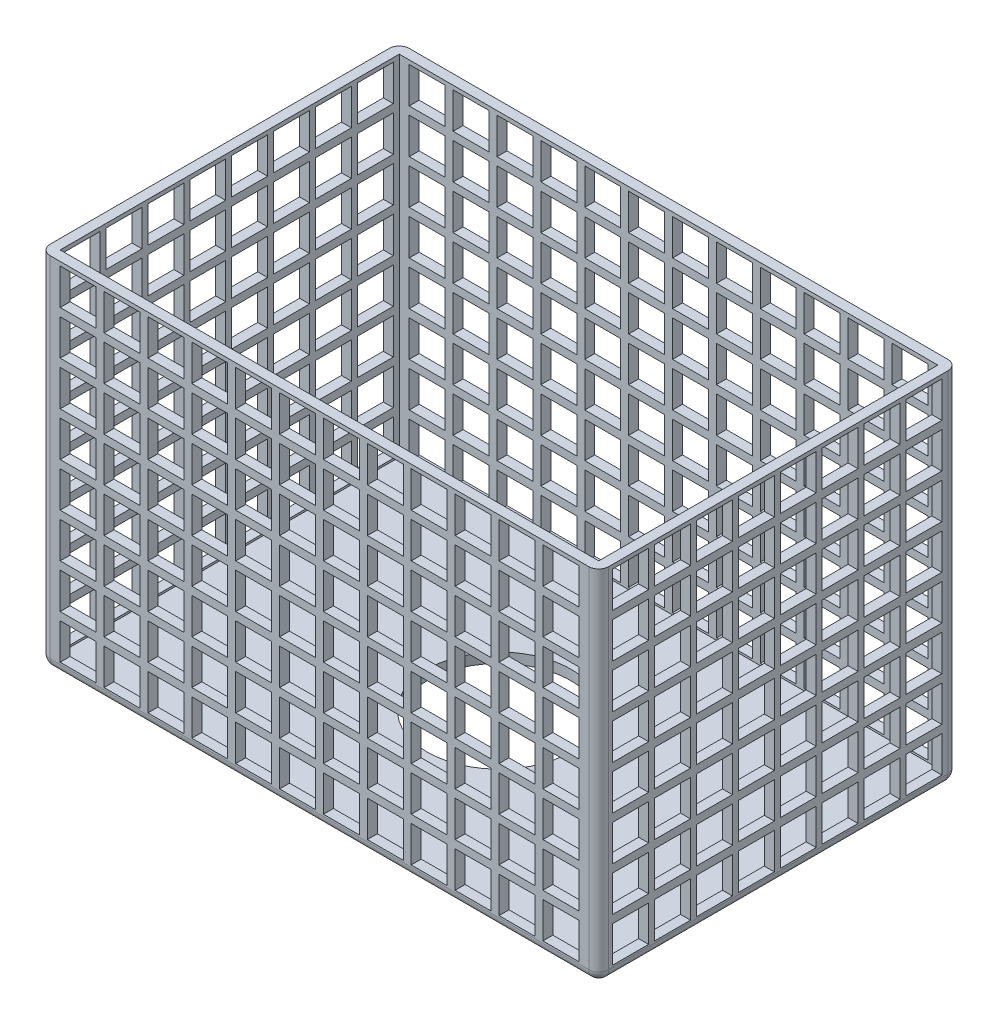
SolidWorks part; units mm, degrees
ref_plane "前视基准面" through (0, 0, 0) normal (0, 0, 1) x (1, 0, 0)
ref_plane "上视基准面" through (0, 0, 0) normal (0, 1, 0) x (1, 0, 0)
ref_plane "右视基准面" through (0, 0, 0) normal (1, 0, 0) x (0, 0, -1)
sketch "草图1" plane through (0, 0, 0) normal (0, 0, 1) x (1, 0, 0)
  line L1 (-140, 90) -> (140, 90)
  line L2 (-140, 90) -> (-140, -90)
  line L3 (-140, -90) -> (140, -90)
  line L4 (140, 90) -> (140, -90)
  line L5 (-140, 90) -> (140, -90) construction
  line L6 (-140, -90) -> (140, 90) construction
  point P0 (0, 0)
  dimension "D1" = 280
  dimension "D2" = 180
extrude "凸台-拉伸1" add sketch "草图1" along normal blind 180
ref_plane "基准面4" through (0, 0, 0) normal (-1, 0, 0) x (0, 0, 1)
ref_plane "基准面5" through (0, 0, 0) normal (0, 1, 0) x (1, 0, 0)
ref_plane "基准面6" through (0, 0, 0) normal (0, 0, -1) x (-1, 0, 0)
fillet "圆角1" radius 5 8 edges at (-140, -90, 90) (-140, 0, 0) (0, -90, 0) (140, 0, 0) (140, -90, 90) (140, 0, 180) (0, -90, 180) (-140, 0, 180)
shell "抽壳1" thickness 5 removed face at (0, 90, 90)
sketch "草图4" plane through (0, 0, 0) normal (0, 0, -1) x (-1, 0, 0)
  line L0 (-135, 90) -> (135, 90) construction
  line L1 (-130, 88) -> (-112, 88)
  line L2 (-130, 88) -> (-130, 70)
  line L3 (-130, 70) -> (-112, 70)
  line L4 (-112, 88) -> (-112, 70)
  line L5 (-135, 90) -> (-135, -85) construction
  line L6 (-108, 88) -> (-108, 70)
  line L7 (-108, 88) -> (-90, 88)
  line L8 (-90, 88) -> (-90, 70)
  line L9 (-108, 70) -> (-90, 70)
  line L10 (-86, 88) -> (-86, 70)
  line L11 (-86, 88) -> (-68, 88)
  line L12 (-68, 88) -> (-68, 70)
  line L13 (-86, 70) -> (-68, 70)
  line L14 (-64, 88) -> (-64, 70)
  line L15 (-64, 88) -> (-46, 88)
  line L16 (-46, 88) -> (-46, 70)
  line L17 (-64, 70) -> (-46, 70)
  line L18 (-42, 88) -> (-42, 70)
  line L19 (-42, 88) -> (-24, 88)
  line L20 (-24, 88) -> (-24, 70)
  line L21 (-42, 70) -> (-24, 70)
  line L22 (-20, 88) -> (-20, 70)
  line L23 (-20, 88) -> (-2, 88)
  line L24 (-2, 88) -> (-2, 70)
  line L25 (-20, 70) -> (-2, 70)
  line L26 (2, 88) -> (2, 70)
  line L27 (2, 88) -> (20, 88)
  line L28 (20, 88) -> (20, 70)
  line L29 (2, 70) -> (20, 70)
  line L30 (24, 88) -> (24, 70)
  line L31 (24, 88) -> (42, 88)
  line L32 (42, 88) -> (42, 70)
  line L33 (24, 70) -> (42, 70)
  line L34 (46, 88) -> (46, 70)
  line L35 (46, 88) -> (64, 88)
  line L36 (64, 88) -> (64, 70)
  line L37 (46, 70) -> (64, 70)
  line L38 (68, 88) -> (68, 70)
  line L39 (68, 88) -> (86, 88)
  line L40 (86, 88) -> (86, 70)
  line L41 (68, 70) -> (86, 70)
  line L42 (90, 88) -> (90, 70)
  line L43 (90, 88) -> (108, 88)
  line L44 (108, 88) -> (108, 70)
  line L45 (90, 70) -> (108, 70)
  line L46 (112, 88) -> (112, 70)
  line L47 (112, 88) -> (130, 88)
  line L48 (130, 88) -> (130, 70)
  line L49 (112, 70) -> (130, 70)
  line L50 (-108, 66) -> (-108, 48)
  line L51 (-108, 66) -> (-90, 66)
  line L52 (-90, 66) -> (-90, 48)
  line L53 (-108, 48) -> (-90, 48)
  line L54 (-86, 66) -> (-86, 48)
  line L55 (-86, 66) -> (-68, 66)
  line L56 (-68, 66) -> (-68, 48)
  line L57 (-86, 48) -> (-68, 48)
  line L58 (-64, 66) -> (-64, 48)
  line L59 (-64, 66) -> (-46, 66)
  line L60 (-46, 66) -> (-46, 48)
  line L61 (-64, 48) -> (-46, 48)
  line L62 (-42, 66) -> (-42, 48)
  line L63 (-42, 66) -> (-24, 66)
  line L64 (-24, 66) -> (-24, 48)
  line L65 (-42, 48) -> (-24, 48)
  line L66 (-20, 66) -> (-20, 48)
  line L67 (-20, 66) -> (-2, 66)
  line L68 (-2, 66) -> (-2, 48)
  line L69 (-20, 48) -> (-2, 48)
  line L70 (2, 66) -> (2, 48)
  line L71 (2, 66) -> (20, 66)
  line L72 (20, 66) -> (20, 48)
  line L73 (2, 48) -> (20, 48)
  line L74 (24, 66) -> (24, 48)
  line L75 (24, 66) -> (42, 66)
  line L76 (42, 66) -> (42, 48)
  line L77 (24, 48) -> (42, 48)
  line L78 (46, 66) -> (46, 48)
  line L79 (46, 66) -> (64, 66)
  line L80 (64, 66) -> (64, 48)
  line L81 (46, 48) -> (64, 48)
  line L82 (68, 66) -> (68, 48)
  line L83 (68, 66) -> (86, 66)
  line L84 (86, 66) -> (86, 48)
  line L85 (68, 48) -> (86, 48)
  line L86 (90, 66) -> (90, 48)
  line L87 (90, 66) -> (108, 66)
  line L88 (108, 66) -> (108, 48)
  line L89 (90, 48) -> (108, 48)
  line L90 (112, 66) -> (112, 48)
  line L91 (112, 66) -> (130, 66)
  line L92 (130, 66) -> (130, 48)
  line L93 (112, 48) -> (130, 48)
  line L94 (-108, 44) -> (-108, 26)
  line L95 (-108, 44) -> (-90, 44)
  line L96 (-90, 44) -> (-90, 26)
  line L97 (-108, 26) -> (-90, 26)
  line L98 (-86, 44) -> (-86, 26)
  line L99 (-86, 44) -> (-68, 44)
  line L100 (-68, 44) -> (-68, 26)
  line L101 (-86, 26) -> (-68, 26)
  line L102 (-64, 44) -> (-64, 26)
  line L103 (-64, 44) -> (-46, 44)
  line L104 (-46, 44) -> (-46, 26)
  line L105 (-64, 26) -> (-46, 26)
  line L106 (-42, 44) -> (-42, 26)
  line L107 (-42, 44) -> (-24, 44)
  line L108 (-24, 44) -> (-24, 26)
  line L109 (-42, 26) -> (-24, 26)
  line L110 (-20, 44) -> (-20, 26)
  line L111 (-20, 44) -> (-2, 44)
  line L112 (-2, 44) -> (-2, 26)
  line L113 (-20, 26) -> (-2, 26)
  line L114 (2, 44) -> (2, 26)
  line L115 (2, 44) -> (20, 44)
  line L116 (20, 44) -> (20, 26)
  line L117 (2, 26) -> (20, 26)
  line L118 (24, 44) -> (24, 26)
  line L119 (24, 44) -> (42, 44)
  line L120 (42, 44) -> (42, 26)
  line L121 (24, 26) -> (42, 26)
  line L122 (46, 44) -> (46, 26)
  line L123 (46, 44) -> (64, 44)
  line L124 (64, 44) -> (64, 26)
  line L125 (46, 26) -> (64, 26)
  line L126 (68, 44) -> (68, 26)
  line L127 (68, 44) -> (86, 44)
  line L128 (86, 44) -> (86, 26)
  line L129 (68, 26) -> (86, 26)
  line L130 (90, 44) -> (90, 26)
  line L131 (90, 44) -> (108, 44)
  line L132 (108, 44) -> (108, 26)
  line L133 (90, 26) -> (108, 26)
  line L134 (112, 44) -> (112, 26)
  line L135 (112, 44) -> (130, 44)
  line L136 (130, 44) -> (130, 26)
  line L137 (112, 26) -> (130, 26)
  line L138 (-108, 22) -> (-108, 4)
  line L139 (-108, 22) -> (-90, 22)
  line L140 (-90, 22) -> (-90, 4)
  line L141 (-108, 4) -> (-90, 4)
  line L142 (-86, 22) -> (-86, 4)
  line L143 (-86, 22) -> (-68, 22)
  line L144 (-68, 22) -> (-68, 4)
  line L145 (-86, 4) -> (-68, 4)
  line L146 (-64, 22) -> (-64, 4)
  line L147 (-64, 22) -> (-46, 22)
  line L148 (-46, 22) -> (-46, 4)
  line L149 (-64, 4) -> (-46, 4)
  line L150 (-42, 22) -> (-42, 4)
  line L151 (-42, 22) -> (-24, 22)
  line L152 (-24, 22) -> (-24, 4)
  line L153 (-42, 4) -> (-24, 4)
  line L154 (-20, 22) -> (-20, 4)
  line L155 (-20, 22) -> (-2, 22)
  line L156 (-2, 22) -> (-2, 4)
  line L157 (-20, 4) -> (-2, 4)
  line L158 (2, 22) -> (2, 4)
  line L159 (2, 22) -> (20, 22)
  line L160 (20, 22) -> (20, 4)
  line L161 (2, 4) -> (20, 4)
  line L162 (24, 22) -> (24, 4)
  line L163 (24, 22) -> (42, 22)
  line L164 (42, 22) -> (42, 4)
  line L165 (24, 4) -> (42, 4)
  line L166 (46, 22) -> (46, 4)
  line L167 (46, 22) -> (64, 22)
  line L168 (64, 22) -> (64, 4)
  line L169 (46, 4) -> (64, 4)
  line L170 (68, 22) -> (68, 4)
  line L171 (68, 22) -> (86, 22)
  line L172 (86, 22) -> (86, 4)
  line L173 (68, 4) -> (86, 4)
  line L174 (90, 22) -> (90, 4)
  line L175 (90, 22) -> (108, 22)
  line L176 (108, 22) -> (108, 4)
  line L177 (90, 4) -> (108, 4)
  line L178 (112, 22) -> (112, 4)
  line L179 (112, 22) -> (130, 22)
  line L180 (130, 22) -> (130, 4)
  line L181 (112, 4) -> (130, 4)
  line L182 (-108, 0) -> (-108, -18)
  line L183 (-108, 0) -> (-90, 0)
  line L184 (-90, 0) -> (-90, -18)
  line L185 (-108, -18) -> (-90, -18)
  line L186 (-86, 0) -> (-86, -18)
  line L187 (-86, 0) -> (-68, 0)
  line L188 (-68, 0) -> (-68, -18)
  line L189 (-86, -18) -> (-68, -18)
  line L190 (-64, 0) -> (-64, -18)
  line L191 (-64, 0) -> (-46, 0)
  line L192 (-46, 0) -> (-46, -18)
  line L193 (-64, -18) -> (-46, -18)
  line L194 (-42, 0) -> (-42, -18)
  line L195 (-42, 0) -> (-24, 0)
  line L196 (-24, 0) -> (-24, -18)
  line L197 (-42, -18) -> (-24, -18)
  line L198 (-20, 0) -> (-20, -18)
  line L199 (-20, 0) -> (-2, 0)
  line L200 (-2, 0) -> (-2, -18)
  line L201 (-20, -18) -> (-2, -18)
  line L202 (2, 0) -> (2, -18)
  line L203 (2, 0) -> (20, 0)
  line L204 (20, 0) -> (20, -18)
  line L205 (2, -18) -> (20, -18)
  line L206 (24, 0) -> (24, -18)
  line L207 (24, 0) -> (42, 0)
  line L208 (42, 0) -> (42, -18)
  line L209 (24, -18) -> (42, -18)
  line L210 (46, 0) -> (46, -18)
  line L211 (46, 0) -> (64, 0)
  line L212 (64, 0) -> (64, -18)
  line L213 (46, -18) -> (64, -18)
  line L214 (68, 0) -> (68, -18)
  line L215 (68, 0) -> (86, 0)
  line L216 (86, 0) -> (86, -18)
  line L217 (68, -18) -> (86, -18)
  line L218 (90, 0) -> (90, -18)
  line L219 (90, 0) -> (108, 0)
  line L220 (108, 0) -> (108, -18)
  line L221 (90, -18) -> (108, -18)
  line L222 (112, 0) -> (112, -18)
  line L223 (112, 0) -> (130, 0)
  line L224 (130, 0) -> (130, -18)
  line L225 (112, -18) -> (130, -18)
  line L226 (-108, -22) -> (-108, -40)
  line L227 (-108, -22) -> (-90, -22)
  line L228 (-90, -22) -> (-90, -40)
  line L229 (-108, -40) -> (-90, -40)
  line L230 (-86, -22) -> (-86, -40)
  line L231 (-86, -22) -> (-68, -22)
  line L232 (-68, -22) -> (-68, -40)
  line L233 (-86, -40) -> (-68, -40)
  line L234 (-64, -22) -> (-64, -40)
  line L235 (-64, -22) -> (-46, -22)
  line L236 (-46, -22) -> (-46, -40)
  line L237 (-64, -40) -> (-46, -40)
  line L238 (-42, -22) -> (-42, -40)
  line L239 (-42, -22) -> (-24, -22)
  line L240 (-24, -22) -> (-24, -40)
  line L241 (-42, -40) -> (-24, -40)
  line L242 (-20, -22) -> (-20, -40)
  line L243 (-20, -22) -> (-2, -22)
  line L244 (-2, -22) -> (-2, -40)
  line L245 (-20, -40) -> (-2, -40)
  line L246 (2, -22) -> (2, -40)
  line L247 (2, -22) -> (20, -22)
  line L248 (20, -22) -> (20, -40)
  line L249 (2, -40) -> (20, -40)
  line L250 (24, -22) -> (24, -40)
  line L251 (24, -22) -> (42, -22)
  line L252 (42, -22) -> (42, -40)
  line L253 (24, -40) -> (42, -40)
  line L254 (46, -22) -> (46, -40)
  line L255 (46, -22) -> (64, -22)
  line L256 (64, -22) -> (64, -40)
  line L257 (46, -40) -> (64, -40)
  line L258 (68, -22) -> (68, -40)
  line L259 (68, -22) -> (86, -22)
  line L260 (86, -22) -> (86, -40)
  line L261 (68, -40) -> (86, -40)
  line L262 (90, -22) -> (90, -40)
  line L263 (90, -22) -> (108, -22)
  line L264 (108, -22) -> (108, -40)
  line L265 (90, -40) -> (108, -40)
  line L266 (112, -22) -> (112, -40)
  line L267 (112, -22) -> (130, -22)
  line L268 (130, -22) -> (130, -40)
  line L269 (112, -40) -> (130, -40)
  line L270 (-108, -44) -> (-108, -62)
  line L271 (-108, -44) -> (-90, -44)
  line L272 (-90, -44) -> (-90, -62)
  line L273 (-108, -62) -> (-90, -62)
  line L274 (-86, -44) -> (-86, -62)
  line L275 (-86, -44) -> (-68, -44)
  line L276 (-68, -44) -> (-68, -62)
  line L277 (-86, -62) -> (-68, -62)
  line L278 (-64, -44) -> (-64, -62)
  line L279 (-64, -44) -> (-46, -44)
  line L280 (-46, -44) -> (-46, -62)
  line L281 (-64, -62) -> (-46, -62)
  line L282 (-42, -44) -> (-42, -62)
  line L283 (-42, -44) -> (-24, -44)
  line L284 (-24, -44) -> (-24, -62)
  line L285 (-42, -62) -> (-24, -62)
  line L286 (-20, -44) -> (-20, -62)
  line L287 (-20, -44) -> (-2, -44)
  line L288 (-2, -44) -> (-2, -62)
  line L289 (-20, -62) -> (-2, -62)
  line L290 (2, -44) -> (2, -62)
  line L291 (2, -44) -> (20, -44)
  line L292 (20, -44) -> (20, -62)
  line L293 (2, -62) -> (20, -62)
  line L294 (24, -44) -> (24, -62)
  line L295 (24, -44) -> (42, -44)
  line L296 (42, -44) -> (42, -62)
  line L297 (24, -62) -> (42, -62)
  line L298 (46, -44) -> (46, -62)
  line L299 (46, -44) -> (64, -44)
  line L300 (64, -44) -> (64, -62)
  line L301 (46, -62) -> (64, -62)
  line L302 (68, -44) -> (68, -62)
  line L303 (68, -44) -> (86, -44)
  line L304 (86, -44) -> (86, -62)
  line L305 (68, -62) -> (86, -62)
  line L306 (90, -44) -> (90, -62)
  line L307 (90, -44) -> (108, -44)
  line L308 (108, -44) -> (108, -62)
  line L309 (90, -62) -> (108, -62)
  line L310 (112, -44) -> (112, -62)
  line L311 (112, -44) -> (130, -44)
  line L312 (130, -44) -> (130, -62)
  line L313 (112, -62) -> (130, -62)
  line L314 (-108, -66) -> (-108, -84)
  line L315 (-108, -66) -> (-90, -66)
  line L316 (-90, -66) -> (-90, -84)
  line L317 (-108, -84) -> (-90, -84)
  line L318 (-86, -66) -> (-86, -84)
  line L319 (-86, -66) -> (-68, -66)
  line L320 (-68, -66) -> (-68, -84)
  line L321 (-86, -84) -> (-68, -84)
  line L322 (-64, -66) -> (-64, -84)
  line L323 (-64, -66) -> (-46, -66)
  line L324 (-46, -66) -> (-46, -84)
  line L325 (-64, -84) -> (-46, -84)
  line L326 (-42, -66) -> (-42, -84)
  line L327 (-42, -66) -> (-24, -66)
  line L328 (-24, -66) -> (-24, -84)
  line L329 (-42, -84) -> (-24, -84)
  line L330 (-20, -66) -> (-20, -84)
  line L331 (-20, -66) -> (-2, -66)
  line L332 (-2, -66) -> (-2, -84)
  line L333 (-20, -84) -> (-2, -84)
  line L334 (2, -66) -> (2, -84)
  line L335 (2, -66) -> (20, -66)
  line L336 (20, -66) -> (20, -84)
  line L337 (2, -84) -> (20, -84)
  line L338 (24, -66) -> (24, -84)
  line L339 (24, -66) -> (42, -66)
  line L340 (42, -66) -> (42, -84)
  line L341 (24, -84) -> (42, -84)
  line L342 (46, -66) -> (46, -84)
  line L343 (46, -66) -> (64, -66)
  line L344 (64, -66) -> (64, -84)
  line L345 (46, -84) -> (64, -84)
  line L346 (68, -66) -> (68, -84)
  line L347 (68, -66) -> (86, -66)
  line L348 (86, -66) -> (86, -84)
  line L349 (68, -84) -> (86, -84)
  line L350 (90, -66) -> (90, -84)
  line L351 (90, -66) -> (108, -66)
  line L352 (108, -66) -> (108, -84)
  line L353 (90, -84) -> (108, -84)
  line L354 (112, -66) -> (112, -84)
  line L355 (112, -66) -> (130, -66)
  line L356 (130, -66) -> (130, -84)
  line L357 (112, -84) -> (130, -84)
  line L358 (-130, 66) -> (-130, 48)
  line L359 (-130, 66) -> (-112, 66)
  line L360 (-112, 66) -> (-112, 48)
  line L361 (-130, 48) -> (-112, 48)
  line L362 (-130, 44) -> (-130, 26)
  line L363 (-130, 44) -> (-112, 44)
  line L364 (-112, 44) -> (-112, 26)
  line L365 (-130, 26) -> (-112, 26)
  line L366 (-130, 22) -> (-130, 4)
  line L367 (-130, 22) -> (-112, 22)
  line L368 (-112, 22) -> (-112, 4)
  line L369 (-130, 4) -> (-112, 4)
  line L370 (-130, 0) -> (-130, -18)
  line L371 (-130, 0) -> (-112, 0)
  line L372 (-112, 0) -> (-112, -18)
  line L373 (-130, -18) -> (-112, -18)
  line L374 (-130, -22) -> (-130, -40)
  line L375 (-130, -22) -> (-112, -22)
  line L376 (-112, -22) -> (-112, -40)
  line L377 (-130, -40) -> (-112, -40)
  line L378 (-130, -44) -> (-130, -62)
  line L379 (-130, -44) -> (-112, -44)
  line L380 (-112, -44) -> (-112, -62)
  line L381 (-130, -62) -> (-112, -62)
  line L382 (-130, -66) -> (-130, -84)
  line L383 (-130, -66) -> (-112, -66)
  line L384 (-112, -66) -> (-112, -84)
  line L385 (-130, -84) -> (-112, -84)
  dimension "D1" = 18
  dimension "D2" = 18
  dimension "D3" = 2
  dimension "D4" = 5
  dimension "D5" = 12
  dimension "D6" = 8
extrude "切除-拉伸3" cut sketch "草图4" against normal through all
sketch "草图5" plane through (140, 0, 0) normal (1, 0, 0) x (0, 0, -1)
  line L0 (-175, 90) -> (-5, 90) construction
  line L1 (-173, 88) -> (-155, 88)
  line L2 (-173, 88) -> (-173, 70)
  line L3 (-173, 70) -> (-155, 70)
  line L4 (-155, 88) -> (-155, 70)
  line L5 (-175, 90) -> (-175, -85) construction
  line L6 (-152, 88) -> (-152, 70)
  line L7 (-152, 88) -> (-134, 88)
  line L8 (-134, 88) -> (-134, 70)
  line L9 (-152, 70) -> (-134, 70)
  line L10 (-131, 88) -> (-131, 70)
  line L11 (-131, 88) -> (-113, 88)
  line L12 (-113, 88) -> (-113, 70)
  line L13 (-131, 70) -> (-113, 70)
  line L14 (-110, 88) -> (-110, 70)
  line L15 (-110, 88) -> (-92, 88)
  line L16 (-92, 88) -> (-92, 70)
  line L17 (-110, 70) -> (-92, 70)
  line L18 (-89, 88) -> (-89, 70)
  line L19 (-89, 88) -> (-71, 88)
  line L20 (-71, 88) -> (-71, 70)
  line L21 (-89, 70) -> (-71, 70)
  line L22 (-68, 88) -> (-68, 70)
  line L23 (-68, 88) -> (-50, 88)
  line L24 (-50, 88) -> (-50, 70)
  line L25 (-68, 70) -> (-50, 70)
  line L26 (-47, 88) -> (-47, 70)
  line L27 (-47, 88) -> (-29, 88)
  line L28 (-29, 88) -> (-29, 70)
  line L29 (-47, 70) -> (-29, 70)
  line L30 (-26, 88) -> (-26, 70)
  line L31 (-26, 88) -> (-8, 88)
  line L32 (-8, 88) -> (-8, 70)
  line L33 (-26, 70) -> (-8, 70)
  line L34 (-152, 66) -> (-152, 48)
  line L35 (-152, 66) -> (-134, 66)
  line L36 (-134, 66) -> (-134, 48)
  line L37 (-152, 48) -> (-134, 48)
  line L38 (-131, 66) -> (-131, 48)
  line L39 (-131, 66) -> (-113, 66)
  line L40 (-113, 66) -> (-113, 48)
  line L41 (-131, 48) -> (-113, 48)
  line L42 (-110, 66) -> (-110, 48)
  line L43 (-110, 66) -> (-92, 66)
  line L44 (-92, 66) -> (-92, 48)
  line L45 (-110, 48) -> (-92, 48)
  line L46 (-89, 66) -> (-89, 48)
  line L47 (-89, 66) -> (-71, 66)
  line L48 (-71, 66) -> (-71, 48)
  line L49 (-89, 48) -> (-71, 48)
  line L50 (-68, 66) -> (-68, 48)
  line L51 (-68, 66) -> (-50, 66)
  line L52 (-50, 66) -> (-50, 48)
  line L53 (-68, 48) -> (-50, 48)
  line L54 (-47, 66) -> (-47, 48)
  line L55 (-47, 66) -> (-29, 66)
  line L56 (-29, 66) -> (-29, 48)
  line L57 (-47, 48) -> (-29, 48)
  line L58 (-26, 66) -> (-26, 48)
  line L59 (-26, 66) -> (-8, 66)
  line L60 (-8, 66) -> (-8, 48)
  line L61 (-26, 48) -> (-8, 48)
  line L62 (-152, 44) -> (-152, 26)
  line L63 (-152, 44) -> (-134, 44)
  line L64 (-134, 44) -> (-134, 26)
  line L65 (-152, 26) -> (-134, 26)
  line L66 (-131, 44) -> (-131, 26)
  line L67 (-131, 44) -> (-113, 44)
  line L68 (-113, 44) -> (-113, 26)
  line L69 (-131, 26) -> (-113, 26)
  line L70 (-110, 44) -> (-110, 26)
  line L71 (-110, 44) -> (-92, 44)
  line L72 (-92, 44) -> (-92, 26)
  line L73 (-110, 26) -> (-92, 26)
  line L74 (-89, 44) -> (-89, 26)
  line L75 (-89, 44) -> (-71, 44)
  line L76 (-71, 44) -> (-71, 26)
  line L77 (-89, 26) -> (-71, 26)
  line L78 (-68, 44) -> (-68, 26)
  line L79 (-68, 44) -> (-50, 44)
  line L80 (-50, 44) -> (-50, 26)
  line L81 (-68, 26) -> (-50, 26)
  line L82 (-47, 44) -> (-47, 26)
  line L83 (-47, 44) -> (-29, 44)
  line L84 (-29, 44) -> (-29, 26)
  line L85 (-47, 26) -> (-29, 26)
  line L86 (-26, 44) -> (-26, 26)
  line L87 (-26, 44) -> (-8, 44)
  line L88 (-8, 44) -> (-8, 26)
  line L89 (-26, 26) -> (-8, 26)
  line L90 (-152, 22) -> (-152, 4)
  line L91 (-152, 22) -> (-134, 22)
  line L92 (-134, 22) -> (-134, 4)
  line L93 (-152, 4) -> (-134, 4)
  line L94 (-131, 22) -> (-131, 4)
  line L95 (-131, 22) -> (-113, 22)
  line L96 (-113, 22) -> (-113, 4)
  line L97 (-131, 4) -> (-113, 4)
  line L98 (-110, 22) -> (-110, 4)
  line L99 (-110, 22) -> (-92, 22)
  line L100 (-92, 22) -> (-92, 4)
  line L101 (-110, 4) -> (-92, 4)
  line L102 (-89, 22) -> (-89, 4)
  line L103 (-89, 22) -> (-71, 22)
  line L104 (-71, 22) -> (-71, 4)
  line L105 (-89, 4) -> (-71, 4)
  line L106 (-68, 22) -> (-68, 4)
  line L107 (-68, 22) -> (-50, 22)
  line L108 (-50, 22) -> (-50, 4)
  line L109 (-68, 4) -> (-50, 4)
  line L110 (-47, 22) -> (-47, 4)
  line L111 (-47, 22) -> (-29, 22)
  line L112 (-29, 22) -> (-29, 4)
  line L113 (-47, 4) -> (-29, 4)
  line L114 (-26, 22) -> (-26, 4)
  line L115 (-26, 22) -> (-8, 22)
  line L116 (-8, 22) -> (-8, 4)
  line L117 (-26, 4) -> (-8, 4)
  line L118 (-152, 0) -> (-152, -18)
  line L119 (-152, 0) -> (-134, 0)
  line L120 (-134, 0) -> (-134, -18)
  line L121 (-152, -18) -> (-134, -18)
  line L122 (-131, 0) -> (-131, -18)
  line L123 (-131, 0) -> (-113, 0)
  line L124 (-113, 0) -> (-113, -18)
  line L125 (-131, -18) -> (-113, -18)
  line L126 (-110, 0) -> (-110, -18)
  line L127 (-110, 0) -> (-92, 0)
  line L128 (-92, 0) -> (-92, -18)
  line L129 (-110, -18) -> (-92, -18)
  line L130 (-89, 0) -> (-89, -18)
  line L131 (-89, 0) -> (-71, 0)
  line L132 (-71, 0) -> (-71, -18)
  line L133 (-89, -18) -> (-71, -18)
  line L134 (-68, 0) -> (-68, -18)
  line L135 (-68, 0) -> (-50, 0)
  line L136 (-50, 0) -> (-50, -18)
  line L137 (-68, -18) -> (-50, -18)
  line L138 (-47, 0) -> (-47, -18)
  line L139 (-47, 0) -> (-29, 0)
  line L140 (-29, 0) -> (-29, -18)
  line L141 (-47, -18) -> (-29, -18)
  line L142 (-26, 0) -> (-26, -18)
  line L143 (-26, 0) -> (-8, 0)
  line L144 (-8, 0) -> (-8, -18)
  line L145 (-26, -18) -> (-8, -18)
  line L146 (-152, -22) -> (-152, -40)
  line L147 (-152, -22) -> (-134, -22)
  line L148 (-134, -22) -> (-134, -40)
  line L149 (-152, -40) -> (-134, -40)
  line L150 (-131, -22) -> (-131, -40)
  line L151 (-131, -22) -> (-113, -22)
  line L152 (-113, -22) -> (-113, -40)
  line L153 (-131, -40) -> (-113, -40)
  line L154 (-110, -22) -> (-110, -40)
  line L155 (-110, -22) -> (-92, -22)
  line L156 (-92, -22) -> (-92, -40)
  line L157 (-110, -40) -> (-92, -40)
  line L158 (-89, -22) -> (-89, -40)
  line L159 (-89, -22) -> (-71, -22)
  line L160 (-71, -22) -> (-71, -40)
  line L161 (-89, -40) -> (-71, -40)
  line L162 (-68, -22) -> (-68, -40)
  line L163 (-68, -22) -> (-50, -22)
  line L164 (-50, -22) -> (-50, -40)
  line L165 (-68, -40) -> (-50, -40)
  line L166 (-47, -22) -> (-47, -40)
  line L167 (-47, -22) -> (-29, -22)
  line L168 (-29, -22) -> (-29, -40)
  line L169 (-47, -40) -> (-29, -40)
  line L170 (-26, -22) -> (-26, -40)
  line L171 (-26, -22) -> (-8, -22)
  line L172 (-8, -22) -> (-8, -40)
  line L173 (-26, -40) -> (-8, -40)
  line L174 (-152, -44) -> (-152, -62)
  line L175 (-152, -44) -> (-134, -44)
  line L176 (-134, -44) -> (-134, -62)
  line L177 (-152, -62) -> (-134, -62)
  line L178 (-131, -44) -> (-131, -62)
  line L179 (-131, -44) -> (-113, -44)
  line L180 (-113, -44) -> (-113, -62)
  line L181 (-131, -62) -> (-113, -62)
  line L182 (-110, -44) -> (-110, -62)
  line L183 (-110, -44) -> (-92, -44)
  line L184 (-92, -44) -> (-92, -62)
  line L185 (-110, -62) -> (-92, -62)
  line L186 (-89, -44) -> (-89, -62)
  line L187 (-89, -44) -> (-71, -44)
  line L188 (-71, -44) -> (-71, -62)
  line L189 (-89, -62) -> (-71, -62)
  line L190 (-68, -44) -> (-68, -62)
  line L191 (-68, -44) -> (-50, -44)
  line L192 (-50, -44) -> (-50, -62)
  line L193 (-68, -62) -> (-50, -62)
  line L194 (-47, -44) -> (-47, -62)
  line L195 (-47, -44) -> (-29, -44)
  line L196 (-29, -44) -> (-29, -62)
  line L197 (-47, -62) -> (-29, -62)
  line L198 (-26, -44) -> (-26, -62)
  line L199 (-26, -44) -> (-8, -44)
  line L200 (-8, -44) -> (-8, -62)
  line L201 (-26, -62) -> (-8, -62)
  line L202 (-152, -66) -> (-152, -84)
  line L203 (-152, -66) -> (-134, -66)
  line L204 (-134, -66) -> (-134, -84)
  line L205 (-152, -84) -> (-134, -84)
  line L206 (-131, -66) -> (-131, -84)
  line L207 (-131, -66) -> (-113, -66)
  line L208 (-113, -66) -> (-113, -84)
  line L209 (-131, -84) -> (-113, -84)
  line L210 (-110, -66) -> (-110, -84)
  line L211 (-110, -66) -> (-92, -66)
  line L212 (-92, -66) -> (-92, -84)
  line L213 (-110, -84) -> (-92, -84)
  line L214 (-89, -66) -> (-89, -84)
  line L215 (-89, -66) -> (-71, -66)
  line L216 (-71, -66) -> (-71, -84)
  line L217 (-89, -84) -> (-71, -84)
  line L218 (-68, -66) -> (-68, -84)
  line L219 (-68, -66) -> (-50, -66)
  line L220 (-50, -66) -> (-50, -84)
  line L221 (-68, -84) -> (-50, -84)
  line L222 (-47, -66) -> (-47, -84)
  line L223 (-47, -66) -> (-29, -66)
  line L224 (-29, -66) -> (-29, -84)
  line L225 (-47, -84) -> (-29, -84)
  line L226 (-26, -66) -> (-26, -84)
  line L227 (-26, -66) -> (-8, -66)
  line L228 (-8, -66) -> (-8, -84)
  line L229 (-26, -84) -> (-8, -84)
  line L230 (-173, 66) -> (-173, 48)
  line L231 (-173, 66) -> (-155, 66)
  line L232 (-155, 66) -> (-155, 48)
  line L233 (-173, 48) -> (-155, 48)
  line L234 (-173, 44) -> (-173, 26)
  line L235 (-173, 44) -> (-155, 44)
  line L236 (-155, 44) -> (-155, 26)
  line L237 (-173, 26) -> (-155, 26)
  line L238 (-173, 22) -> (-173, 4)
  line L239 (-173, 22) -> (-155, 22)
  line L240 (-155, 22) -> (-155, 4)
  line L241 (-173, 4) -> (-155, 4)
  line L242 (-173, 0) -> (-173, -18)
  line L243 (-173, 0) -> (-155, 0)
  line L244 (-155, 0) -> (-155, -18)
  line L245 (-173, -18) -> (-155, -18)
  line L246 (-173, -22) -> (-173, -40)
  line L247 (-173, -22) -> (-155, -22)
  line L248 (-155, -22) -> (-155, -40)
  line L249 (-173, -40) -> (-155, -40)
  line L250 (-173, -44) -> (-173, -62)
  line L251 (-173, -44) -> (-155, -44)
  line L252 (-155, -44) -> (-155, -62)
  line L253 (-173, -62) -> (-155, -62)
  line L254 (-173, -66) -> (-173, -84)
  line L255 (-173, -66) -> (-155, -66)
  line L256 (-155, -66) -> (-155, -84)
  line L257 (-173, -84) -> (-155, -84)
  dimension "D1" = 18
  dimension "D2" = 18
  dimension "D3" = 2
  dimension "D4" = 2
  dimension "D5" = 8
  dimension "D6" = 8
extrude "切除-拉伸4" cut sketch "草图5" against normal through all
ref_plane "基准面7" through (0, 0, 90) normal (0, 0, 1) x (1, 0, 0)
ref_axis "基准轴1" through (0, 98.75, 90) along (0, -1, 0)
ref_point "点1"
sketch "草图6" plane through (0, -85, 0) normal (0, 1, 0) x (1, 0, 0)
  circle A0 centre (0, -90) radius 36
extrude "切除-拉伸5" cut sketch "草图6" against normal through all contours A0
